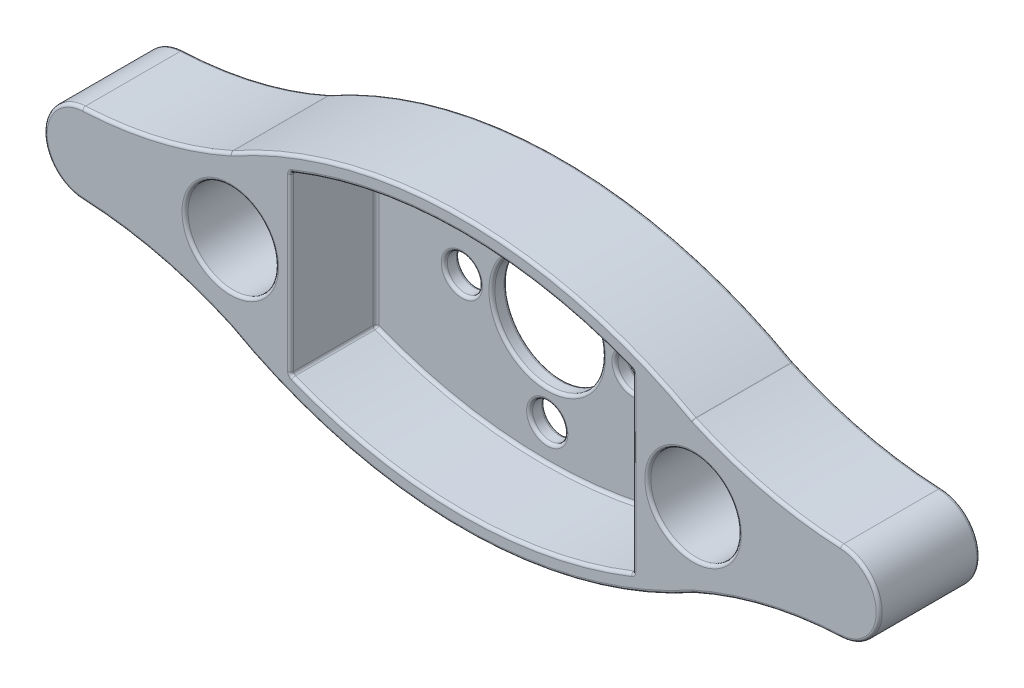
SolidWorks part; units mm, degrees
material "ABS"
ref_plane "Plano frontal" through (0, 0, 0) normal (0, 0, 1) x (1, 0, 0)
ref_plane "Plano superior" through (0, 0, 0) normal (0, 1, 0) x (1, 0, 0)
ref_plane "Plano direito" through (0, 0, 0) normal (1, 0, 0) x (0, 0, -1)
sketch "Esboço1" plane through (0, 0, 0) normal (0, 0, 1) x (1, 0, 0)
  line L0 (0, -5.5) -> (0, 5.5) construction
  line L1 (0, 0) -> (37.5, 0) construction
  line L2 (23, -4.5) -> (23, -7.5) construction
  line L3 (0, 13.5) -> (0, -13.5) construction
  circle A0 centre (0, 0) radius 5.5
  circle A1 centre (23, 0) radius 4.5
  arc A2 (0, 13.5) -> (0, -13.5) centre (0, 0) ccw construction
  arc A3 (37.6782, -3.996) -> (37.6782, 3.996) centre (37.5, 0) ccw
  arc A4 (37.6782, -3.996) -> (23, -7.5) centre (39.4602, -43.9563) ccw
  arc A5 (23, -7.5) -> (-23, -7.5) centre (0, 33.5833) cw
  arc A6 (37.6782, 3.996) -> (23, 7.5) centre (39.4602, 43.9563) cw
  arc A7 (23, 7.5) -> (-23, 7.5) centre (0, -33.5833) ccw
  circle A8 centre (-23, 0) radius 4.5
  arc A9 (-37.6782, 3.996) -> (-23, 7.5) centre (-39.4602, 43.9563) ccw
  arc A10 (-37.6782, -3.996) -> (-37.6782, 3.996) centre (-37.5, 0) cw
  arc A11 (-37.6782, -3.996) -> (-23, -7.5) centre (-39.4602, -43.9563) cw
  dimension "D1" = 11
  dimension "D3" = 9
  dimension "D4" = 27
  dimension "D6" = 8
  dimension "D8" = 40
  dimension "D2" = 23
  dimension "D5" = 37.5
  dimension "D7" = 3
  dimension "D9" = 27
extrude "Ressalto-extrusão1" add sketch "Esboço1" along normal blind 10
sketch "Esboço2" plane through (0, 0, 10) normal (0, 0, 1) x (1, 0, 0)
  line L0 (0, 12.3483) -> (0, 13.5) construction
  line L1 (17, 0) -> (17, 8.7114)
  line L2 (17, 0) -> (17, -8.7114)
  line L3 (-17, 0) -> (-17, 8.7114)
  line L4 (-17, 0) -> (-17, -8.7114)
  arc A1 (23, 7.5) -> (-23, 7.5) centre (0, -33.5833) ccw construction
  circle A68 centre (-23, 0) radius 6
  circle A69 centre (-23, 0) radius 6 construction
  circle A71 centre (23, 0) radius 6
  circle A72 centre (23, 0) radius 6 construction
  arc A74 (-22.3227, -6.16) -> (22.3227, -6.16) centre (0, 33.5833) ccw
  arc A75 (37.6114, -2.4975) -> (22.3227, -6.16) centre (39.4602, -43.9563) ccw
  arc A76 (37.6114, -2.4975) -> (37.6114, 2.4975) centre (37.5, 0) ccw
  arc A77 (22.3227, 6.16) -> (37.6114, 2.4975) centre (39.4602, 43.9563) ccw
  arc A78 (22.3227, 6.16) -> (-22.3227, 6.16) centre (0, -33.5833) ccw
  arc A79 (-37.6114, 2.4975) -> (-22.3227, 6.16) centre (-39.4602, 43.9563) ccw
  arc A80 (-37.6114, 2.4975) -> (-37.6114, -2.4975) centre (-37.5, 0) ccw
  arc A81 (-22.3227, -6.16) -> (-37.6114, -2.4975) centre (-39.4602, -43.9563) ccw
  arc A82 (-22.3227, -6.16) -> (22.3227, -6.16) centre (0, 33.5833) ccw
  arc A83 (37.6114, -2.4975) -> (22.3227, -6.16) centre (39.4602, -43.9563) ccw
  arc A84 (37.6114, -2.4975) -> (37.6114, 2.4975) centre (37.5, 0) ccw
  arc A85 (22.3227, 6.16) -> (37.6114, 2.4975) centre (39.4602, 43.9563) ccw
  arc A86 (22.3227, 6.16) -> (-22.3227, 6.16) centre (0, -33.5833) ccw
  arc A87 (-37.6114, 2.4975) -> (-22.3227, 6.16) centre (-39.4602, 43.9563) ccw
  arc A88 (-37.6114, 2.4975) -> (-37.6114, -2.4975) centre (-37.5, 0) ccw
  arc A89 (-22.3227, -6.16) -> (-37.6114, -2.4975) centre (-39.4602, -43.9563) ccw
  circle M11 centre (0, 0) radius 5.5
  dimension "D1" = 1.5
  dimension "D2" = 1.5
  dimension "D3" = 1.5
extrude "Corte-extrusão1" cut sketch "Esboço2" against normal blind 8.5 contours L1 A86 L3 L4 A82 L2 M11 region at (16.5838, -4.3557, 10)
sketch "Esboço3" plane through (0, 0, 0) normal (0, 0, -1) x (-1, 0, 0)
  circle A0 centre (0, 8.485) radius 1.75
  circle A1 centre (8.485, 0) radius 1.75
  circle A2 centre (0, -8.485) radius 1.75
  circle A3 centre (-8.485, 0) radius 1.75
  point P12 (0, 0)
  dimension "D1" = 3.5
  dimension "D2" = 8.485
  dimension "D4" = 8.485
  dimension "D5" = 8.485
  dimension "D3" = 4
extrude "Corte-extrusão2" cut sketch "Esboço3" against normal blind 8.5
fillet "Filete1" radius 0.3 46 edges at (6.735, 0, 0) (-1.75, -8.485, 0) (-10.235, 0, 0) (-1.75, 8.485, 0) (10.235, 0, 1.5) (1.75, -8.485, 1.5) (-6.735, 0, 1.5) (1.75, 8.485, 1.5) (17, 0, 10) (0, 12, 10) (-17, 0, 10) (0, -12, 10) (5.5, 0, 1.5) (17, 0, 1.5) (0, 12, 1.5) (-17, 0, 1.5) (0, -12, 1.5) (17, 8.7114, 5.75) (-17, 8.7114, 5.75) (-17, -8.7114, 5.75) (17, -8.7114, 5.75) (-27.5, 0, 0) (-27.5, 0, 10) (27.5, 0, 0) (27.5, 0, 10) (5.5, 0, 0) (30.1724, -5.0495, 0) (41.5, 0, 0) (30.1724, 5.0495, 0) (0, 13.5, 0) (-30.1724, 5.0495, 0) (-41.5, 0, 0) (-30.1724, -5.0495, 0) (30.1724, -5.0495, 10) (41.5, 0, 10) (30.1724, 5.0495, 10) (0, 13.5, 10) (-30.1724, 5.0495, 10) (-41.5, 0, 10) (-30.1724, -5.0495, 10) (0, -13.5, 10) (23, -7.5, 5) (-23, -7.5, 5) (-23, 7.5, 5) (23, 7.5, 5) (0, -13.5, 0)
equation "\"D5@Esboço3\"=\"D2@Esboço3\""
equation "\"D4@Esboço3\"=\"D2@Esboço3\""
